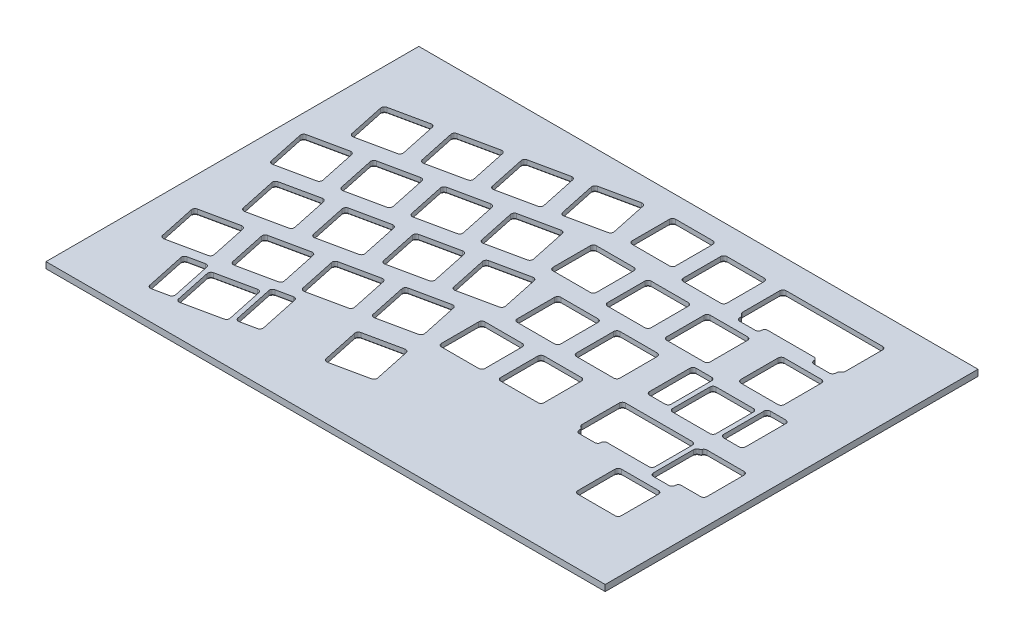
SolidWorks part; units mm, degrees
ref_plane "Front Plane" through (0, 0, 0) normal (0, 0, 1) x (1, 0, 0)
ref_plane "Top Plane" through (0, 0, 0) normal (0, 1, 0) x (1, 0, 0)
ref_plane "Right Plane" through (0, 0, 0) normal (1, 0, 0) x (0, 0, -1)
sketch "Sketch1" plane through (0, 0, 0) normal (0, 1, 0) x (1, 0, 0)
  line L1 (-5, -3) -> (175, -3)
  line L2 (-5, -3) -> (-5, 117)
  line L3 (-5, 117) -> (175, 117)
  line L4 (175, -3) -> (175, 117)
  line L5 (-5, -3) -> (175, 117) construction
  line L6 (-5, 117) -> (175, -3) construction
  point P5 (85, 57)
  line B0 (3.9344, 34.8314) -> (6.4293, 23.0936)
  line B1 (7.6154, 22.3234) -> (19.3531, 24.8183)
  line B2 (17.6284, 37.7422) -> (20.1234, 26.0044)
  line B3 (4.7046, 36.0175) -> (16.4424, 38.5124)
  line B4 (9.2944, 55.4414) -> (11.7893, 43.7036)
  line B5 (12.9754, 42.9334) -> (24.7131, 45.4283)
  line B6 (22.9884, 58.3522) -> (25.4834, 46.6144)
  line B7 (10.0646, 56.6275) -> (21.8024, 59.1224)
  line B8 (0.6744, 73.0914) -> (3.1693, 61.3536)
  line B9 (4.3554, 60.5834) -> (16.0931, 63.0783)
  line B10 (14.3684, 76.0022) -> (16.8634, 64.2644)
  line B11 (1.4446, 74.2775) -> (13.1824, 76.7724)
  line B12 (6.0344, 93.7014) -> (8.5293, 81.9636)
  line B13 (9.7154, 81.1934) -> (21.4531, 83.6883)
  line B14 (19.7284, 96.6122) -> (22.2234, 84.8744)
  line B15 (6.8046, 94.8875) -> (18.5424, 97.3824)
  line B16 (22.5681, 38.7921) -> (25.063, 27.0543)
  line B17 (26.2491, 26.2841) -> (37.9868, 28.7791)
  line B18 (36.2621, 41.7029) -> (38.7571, 29.9651)
  line B19 (23.3383, 39.9782) -> (35.0761, 42.4731)
  line B20 (27.9281, 59.4021) -> (30.423, 47.6643)
  line B21 (31.6091, 46.8941) -> (43.3468, 49.3891)
  line B22 (41.6221, 62.3129) -> (44.1171, 50.5751)
  line B23 (28.6983, 60.5882) -> (40.4361, 63.0831)
  line B24 (19.3081, 77.0521) -> (21.803, 65.3143)
  line B25 (22.9891, 64.5441) -> (34.7268, 67.0391)
  line B26 (33.0021, 79.9629) -> (35.4971, 68.2251)
  line B27 (20.0783, 78.2382) -> (31.8161, 80.7331)
  line B28 (24.6681, 97.6621) -> (27.163, 85.9243)
  line B29 (28.3491, 85.1541) -> (40.0868, 87.6491)
  line B30 (38.3621, 100.5729) -> (40.8571, 88.8351)
  line B31 (25.4383, 98.8482) -> (37.1761, 101.3431)
  line B32 (41.2018, 42.7528) -> (43.6967, 31.0151)
  line B33 (44.8828, 30.2448) -> (56.6206, 32.7398)
  line B34 (54.8959, 45.6636) -> (57.3908, 33.9258)
  line B35 (41.972, 43.9389) -> (53.7098, 46.4338)
  line B36 (46.5618, 63.3628) -> (49.0567, 51.6251)
  line B37 (50.2428, 50.8548) -> (61.9806, 53.3498)
  line B38 (60.2559, 66.2736) -> (62.7508, 54.5358)
  line B39 (47.332, 64.5489) -> (59.0698, 67.0438)
  line B40 (37.9418, 81.0128) -> (40.4367, 69.2751)
  line B41 (41.6228, 68.5048) -> (53.3606, 70.9998)
  line B42 (51.6359, 83.9236) -> (54.1308, 72.1858)
  line B43 (38.712, 82.1989) -> (50.4498, 84.6938)
  line B44 (43.3018, 101.6228) -> (45.7967, 89.8851)
  line B45 (46.9828, 89.1148) -> (58.7206, 91.6098)
  line B46 (56.9959, 104.5336) -> (59.4908, 92.7958)
  line B47 (44.072, 102.8089) -> (55.8098, 105.3038)
  line B48 (24.2355, 19.6636) -> (26.7304, 7.9258)
  line B49 (27.9165, 7.1555) -> (39.6543, 9.6505)
  line B50 (37.9296, 22.5743) -> (40.4245, 10.8365)
  line B51 (25.0057, 20.8496) -> (36.7435, 23.3446)
  line B52 (64.6455, 26.7236) -> (67.1404, 14.9858)
  line B53 (68.3265, 14.2155) -> (80.0643, 16.7105)
  line B54 (78.3396, 29.6343) -> (80.8345, 17.8965)
  line B55 (65.4157, 27.9096) -> (77.1535, 30.4046)
  line B56 (59.8355, 46.7136) -> (62.3304, 34.9758)
  line B57 (63.5165, 34.2055) -> (75.2543, 36.7005)
  line B58 (73.5296, 49.6243) -> (76.0245, 37.8865)
  line B59 (60.6057, 47.8996) -> (72.3435, 50.3946)
  line B60 (65.1955, 67.3236) -> (67.6904, 55.5858)
  line B61 (68.8765, 54.8155) -> (80.6143, 57.3105)
  line B62 (78.8896, 70.2343) -> (81.3845, 58.4965)
  line B63 (65.9657, 68.5096) -> (77.7035, 71.0046)
  line B64 (61.9355, 105.5836) -> (64.4304, 93.8458)
  line B65 (65.6165, 93.0755) -> (77.3543, 95.5705)
  line B66 (75.6296, 108.4943) -> (78.1245, 96.7565)
  line B67 (62.7057, 106.7696) -> (74.4435, 109.2646)
  line B68 (56.5755, 84.9736) -> (59.0704, 73.2358)
  line B69 (60.2565, 72.4655) -> (71.9943, 74.9605)
  line B70 (70.2696, 87.8843) -> (72.7645, 76.1465)
  line B71 (57.3457, 86.1596) -> (69.0835, 88.6546)
  line B72 (83.53, 109.15) -> (83.53, 97.15)
  line B73 (84.53, 96.15) -> (96.53, 96.15)
  line B74 (97.53, 109.15) -> (97.53, 97.15)
  line B75 (84.53, 110.15) -> (96.53, 110.15)
  line B76 (102.16, 107.01) -> (102.16, 95.01)
  line B77 (103.16, 94.01) -> (115.16, 94.01)
  line B78 (116.16, 107.01) -> (116.16, 95.01)
  line B79 (103.16, 108.01) -> (115.16, 108.01)
  line B80 (139.67, 87.96) -> (139.67, 75.96)
  line B81 (140.67, 74.96) -> (152.67, 74.96)
  line B82 (153.67, 87.96) -> (153.67, 75.96)
  line B83 (140.67, 88.96) -> (152.67, 88.96)
  line B84 (78.17, 89.02) -> (78.17, 77.02)
  line B85 (79.17, 76.02) -> (91.17, 76.02)
  line B86 (92.17, 89.02) -> (92.17, 77.02)
  line B87 (79.17, 90.02) -> (91.17, 90.02)
  line B88 (115.85, 87.96) -> (115.85, 75.96)
  line B89 (116.85, 74.96) -> (128.85, 74.96)
  line B90 (129.85, 87.96) -> (129.85, 75.96)
  line B91 (116.85, 88.96) -> (128.85, 88.96)
  line B92 (86.79, 68.91) -> (86.79, 56.91)
  line B93 (87.79, 55.91) -> (99.79, 55.91)
  line B94 (100.79, 68.91) -> (100.79, 56.91)
  line B95 (87.79, 69.91) -> (99.79, 69.91)
  line B96 (96.8, 87.96) -> (96.8, 75.96)
  line B97 (97.8, 74.96) -> (109.8, 74.96)
  line B98 (110.8, 87.96) -> (110.8, 75.96)
  line B99 (97.8, 88.96) -> (109.8, 88.96)
  line B100 (81.43, 49.86) -> (81.43, 37.86)
  line B101 (82.43, 36.86) -> (94.43, 36.86)
  line B102 (95.43, 49.86) -> (95.43, 37.86)
  line B103 (82.43, 50.86) -> (94.43, 50.86)
  line B104 (136.79, 68.91) -> (136.79, 56.91)
  line B105 (137.79, 55.91) -> (149.79, 55.91)
  line B106 (150.79, 68.91) -> (150.79, 56.91)
  line B107 (137.79, 69.91) -> (149.79, 69.91)
  line B108 (105.84, 68.91) -> (105.84, 56.91)
  line B109 (106.84, 55.91) -> (118.84, 55.91)
  line B110 (119.84, 68.91) -> (119.84, 56.91)
  line B111 (106.84, 69.91) -> (118.84, 69.91)
  line B112 (144.4256, 30.762) -> (144.4256, 18.762)
  line B113 (145.4256, 17.762) -> (157.4256, 17.762)
  line B114 (158.4256, 30.762) -> (158.4256, 18.762)
  line B115 (145.4256, 31.762) -> (157.4256, 31.762)
  line B116 (100.48, 49.86) -> (100.48, 37.86)
  line B117 (101.48, 36.86) -> (113.48, 36.86)
  line B118 (114.48, 49.86) -> (114.48, 37.86)
  line B119 (101.48, 50.86) -> (113.48, 50.86)
  line B120 (151.638, 48.86) -> (151.638, 35.86)
  line B121 (152.638, 34.86) -> (157.638, 34.86)
  line B122 (158.638, 35.86) -> (158.638, 36.86)
  line B123 (158.638, 36.86) -> (165.8688, 36.86)
  line B124 (166.8688, 49.86) -> (166.8688, 37.86)
  line B125 (153.8688, 50.86) -> (165.8688, 50.86)
  line B126 (152.8688, 49.86) -> (152.638, 49.86)
  line B127 (128.762, 34.86) -> (133.762, 34.86)
  line B128 (134.762, 35.86) -> (134.762, 36.86)
  line B129 (134.762, 36.86) -> (149.2, 36.86)
  line B130 (150.2, 49.86) -> (150.2, 37.86)
  line B131 (127.675, 50.86) -> (149.2, 50.86)
  line B132 (126.675, 49.86) -> (126.675, 37.86)
  line B133 (127.675, 36.86) -> (127.762, 36.86)
  line B134 (127.762, 36.86) -> (127.762, 35.86)
  line B135 (15.5661, 19.8655) -> (18.2689, 7.1496)
  line B136 (19.455, 6.3793) -> (24.3457, 7.4189)
  line B137 (25.1159, 8.605) -> (22.4131, 21.3209)
  line B138 (21.227, 22.0911) -> (16.3363, 21.0515)
  line B139 (38.9203, 24.8296) -> (41.6232, 12.1137)
  line B140 (42.8092, 11.3434) -> (47.7, 12.383)
  line B141 (48.4702, 13.5691) -> (45.7673, 26.285)
  line B142 (44.5813, 27.0552) -> (39.6906, 26.0156)
  line B143 (128.352, 70.91) -> (128.352, 57.91)
  line B144 (129.352, 56.91) -> (134.352, 56.91)
  line B145 (135.352, 57.91) -> (135.352, 70.91)
  line B146 (134.352, 71.91) -> (129.352, 71.91)
  line B147 (147.173, 92.01) -> (152.173, 92.01)
  line B148 (153.173, 93.01) -> (153.173, 94.01)
  line B149 (153.173, 94.01) -> (153.26, 94.01)
  line B150 (154.26, 107.01) -> (154.26, 95.01)
  line B151 (122.21, 108.01) -> (153.26, 108.01)
  line B152 (121.21, 107.01) -> (121.21, 95.01)
  line B153 (122.21, 94.01) -> (122.297, 94.01)
  line B154 (122.297, 94.01) -> (122.297, 93.01)
  line B155 (123.297, 92.01) -> (128.297, 92.01)
  line B156 (129.297, 93.01) -> (129.297, 94.01)
  line B157 (129.297, 94.01) -> (146.173, 94.01)
  line B158 (146.173, 94.01) -> (146.173, 93.01)
  line B159 (152.228, 70.91) -> (152.228, 57.91)
  line B160 (153.228, 56.91) -> (158.228, 56.91)
  line B161 (159.228, 57.91) -> (159.228, 70.91)
  line B162 (158.228, 71.91) -> (153.228, 71.91)
  arc B163 (6.4293, 23.0936) -> (7.6154, 22.3234) centre (7.4074, 23.3015) ccw
  arc B164 (19.3531, 24.8183) -> (20.1234, 26.0044) centre (19.1452, 25.7965) ccw
  arc B165 (17.6284, 37.7422) -> (16.4424, 38.5124) centre (16.6503, 37.5343) ccw
  arc B166 (4.7046, 36.0175) -> (3.9344, 34.8314) centre (4.9125, 35.0393) ccw
  arc B167 (11.7893, 43.7036) -> (12.9754, 42.9334) centre (12.7674, 43.9115) ccw
  arc B168 (24.7131, 45.4283) -> (25.4834, 46.6144) centre (24.5052, 46.4065) ccw
  arc B169 (22.9884, 58.3522) -> (21.8024, 59.1224) centre (22.0103, 58.1443) ccw
  arc B170 (10.0646, 56.6275) -> (9.2944, 55.4414) centre (10.2725, 55.6493) ccw
  arc B171 (3.1693, 61.3536) -> (4.3554, 60.5834) centre (4.1474, 61.5615) ccw
  arc B172 (16.0931, 63.0783) -> (16.8634, 64.2644) centre (15.8852, 64.0565) ccw
  arc B173 (14.3684, 76.0022) -> (13.1824, 76.7724) centre (13.3903, 75.7943) ccw
  arc B174 (1.4446, 74.2775) -> (0.6744, 73.0914) centre (1.6525, 73.2993) ccw
  arc B175 (8.5293, 81.9636) -> (9.7154, 81.1934) centre (9.5074, 82.1715) ccw
  arc B176 (21.4531, 83.6883) -> (22.2234, 84.8744) centre (21.2452, 84.6665) ccw
  arc B177 (19.7284, 96.6122) -> (18.5424, 97.3824) centre (18.7503, 96.4043) ccw
  arc B178 (6.8046, 94.8875) -> (6.0344, 93.7014) centre (7.0125, 93.9093) ccw
  arc B179 (25.063, 27.0543) -> (26.2491, 26.2841) centre (26.0412, 27.2623) ccw
  arc B180 (37.9868, 28.7791) -> (38.7571, 29.9651) centre (37.7789, 29.7572) ccw
  arc B181 (36.2621, 41.7029) -> (35.0761, 42.4731) centre (35.284, 41.495) ccw
  arc B182 (23.3383, 39.9782) -> (22.5681, 38.7921) centre (23.5462, 39) ccw
  arc B183 (30.423, 47.6643) -> (31.6091, 46.8941) centre (31.4012, 47.8723) ccw
  arc B184 (43.3468, 49.3891) -> (44.1171, 50.5751) centre (43.1389, 50.3672) ccw
  arc B185 (41.6221, 62.3129) -> (40.4361, 63.0831) centre (40.644, 62.105) ccw
  arc B186 (28.6983, 60.5882) -> (27.9281, 59.4021) centre (28.9062, 59.61) ccw
  arc B187 (21.803, 65.3143) -> (22.9891, 64.5441) centre (22.7812, 65.5223) ccw
  arc B188 (34.7268, 67.0391) -> (35.4971, 68.2251) centre (34.5189, 68.0172) ccw
  arc B189 (33.0021, 79.9629) -> (31.8161, 80.7331) centre (32.024, 79.755) ccw
  arc B190 (20.0783, 78.2382) -> (19.3081, 77.0521) centre (20.2862, 77.26) ccw
  arc B191 (27.163, 85.9243) -> (28.3491, 85.1541) centre (28.1412, 86.1323) ccw
  arc B192 (40.0868, 87.6491) -> (40.8571, 88.8351) centre (39.8789, 88.6272) ccw
  arc B193 (38.3621, 100.5729) -> (37.1761, 101.3431) centre (37.384, 100.365) ccw
  arc B194 (25.4383, 98.8482) -> (24.6681, 97.6621) centre (25.6462, 97.87) ccw
  arc B195 (43.6967, 31.0151) -> (44.8828, 30.2448) centre (44.6749, 31.223) ccw
  arc B196 (56.6206, 32.7398) -> (57.3908, 33.9258) centre (56.4126, 33.7179) ccw
  arc B197 (54.8959, 45.6636) -> (53.7098, 46.4338) centre (53.9177, 45.4557) ccw
  arc B198 (41.972, 43.9389) -> (41.2018, 42.7528) centre (42.1799, 42.9607) ccw
  arc B199 (49.0567, 51.6251) -> (50.2428, 50.8548) centre (50.0349, 51.833) ccw
  arc B200 (61.9806, 53.3498) -> (62.7508, 54.5358) centre (61.7726, 54.3279) ccw
  arc B201 (60.2559, 66.2736) -> (59.0698, 67.0438) centre (59.2777, 66.0657) ccw
  arc B202 (47.332, 64.5489) -> (46.5618, 63.3628) centre (47.5399, 63.5707) ccw
  arc B203 (40.4367, 69.2751) -> (41.6228, 68.5048) centre (41.4149, 69.483) ccw
  arc B204 (53.3606, 70.9998) -> (54.1308, 72.1858) centre (53.1526, 71.9779) ccw
  arc B205 (51.6359, 83.9236) -> (50.4498, 84.6938) centre (50.6577, 83.7157) ccw
  arc B206 (38.712, 82.1989) -> (37.9418, 81.0128) centre (38.9199, 81.2207) ccw
  arc B207 (45.7967, 89.8851) -> (46.9828, 89.1148) centre (46.7749, 90.093) ccw
  arc B208 (58.7206, 91.6098) -> (59.4908, 92.7958) centre (58.5126, 92.5879) ccw
  arc B209 (56.9959, 104.5336) -> (55.8098, 105.3038) centre (56.0177, 104.3257) ccw
  arc B210 (44.072, 102.8089) -> (43.3018, 101.6228) centre (44.2799, 101.8307) ccw
  arc B211 (26.7304, 7.9258) -> (27.9165, 7.1555) centre (27.7086, 8.1337) ccw
  arc B212 (39.6543, 9.6505) -> (40.4245, 10.8365) centre (39.4464, 10.6286) ccw
  arc B213 (37.9296, 22.5743) -> (36.7435, 23.3446) centre (36.9514, 22.3664) ccw
  arc B214 (25.0057, 20.8496) -> (24.2355, 19.6636) centre (25.2136, 19.8715) ccw
  arc B215 (67.1404, 14.9858) -> (68.3265, 14.2155) centre (68.1186, 15.1937) ccw
  arc B216 (80.0643, 16.7105) -> (80.8345, 17.8965) centre (79.8564, 17.6886) ccw
  arc B217 (78.3396, 29.6343) -> (77.1535, 30.4046) centre (77.3614, 29.4264) ccw
  arc B218 (65.4157, 27.9096) -> (64.6455, 26.7236) centre (65.6236, 26.9315) ccw
  arc B219 (62.3304, 34.9758) -> (63.5165, 34.2055) centre (63.3086, 35.1837) ccw
  arc B220 (75.2543, 36.7005) -> (76.0245, 37.8865) centre (75.0464, 37.6786) ccw
  arc B221 (73.5296, 49.6243) -> (72.3435, 50.3946) centre (72.5514, 49.4164) ccw
  arc B222 (60.6057, 47.8996) -> (59.8355, 46.7136) centre (60.8136, 46.9215) ccw
  arc B223 (67.6904, 55.5858) -> (68.8765, 54.8155) centre (68.6686, 55.7937) ccw
  arc B224 (80.6143, 57.3105) -> (81.3845, 58.4965) centre (80.4064, 58.2886) ccw
  arc B225 (78.8896, 70.2343) -> (77.7035, 71.0046) centre (77.9114, 70.0264) ccw
  arc B226 (65.9657, 68.5096) -> (65.1955, 67.3236) centre (66.1736, 67.5315) ccw
  arc B227 (64.4304, 93.8458) -> (65.6165, 93.0755) centre (65.4086, 94.0537) ccw
  arc B228 (77.3543, 95.5705) -> (78.1245, 96.7565) centre (77.1464, 96.5486) ccw
  arc B229 (75.6296, 108.4943) -> (74.4435, 109.2646) centre (74.6514, 108.2864) ccw
  arc B230 (62.7057, 106.7696) -> (61.9355, 105.5836) centre (62.9136, 105.7915) ccw
  arc B231 (59.0704, 73.2358) -> (60.2565, 72.4655) centre (60.0486, 73.4437) ccw
  arc B232 (71.9943, 74.9605) -> (72.7645, 76.1465) centre (71.7864, 75.9386) ccw
  arc B233 (70.2696, 87.8843) -> (69.0835, 88.6546) centre (69.2914, 87.6764) ccw
  arc B234 (57.3457, 86.1596) -> (56.5755, 84.9736) centre (57.5536, 85.1815) ccw
  arc B235 (83.53, 97.15) -> (84.53, 96.15) centre (84.53, 97.15) ccw
  arc B236 (96.53, 96.15) -> (97.53, 97.15) centre (96.53, 97.15) ccw
  arc B237 (97.53, 109.15) -> (96.53, 110.15) centre (96.53, 109.15) ccw
  arc B238 (84.53, 110.15) -> (83.53, 109.15) centre (84.53, 109.15) ccw
  arc B239 (102.16, 95.01) -> (103.16, 94.01) centre (103.16, 95.01) ccw
  arc B240 (115.16, 94.01) -> (116.16, 95.01) centre (115.16, 95.01) ccw
  arc B241 (116.16, 107.01) -> (115.16, 108.01) centre (115.16, 107.01) ccw
  arc B242 (103.16, 108.01) -> (102.16, 107.01) centre (103.16, 107.01) ccw
  arc B243 (139.67, 75.96) -> (140.67, 74.96) centre (140.67, 75.96) ccw
  arc B244 (152.67, 74.96) -> (153.67, 75.96) centre (152.67, 75.96) ccw
  arc B245 (153.67, 87.96) -> (152.67, 88.96) centre (152.67, 87.96) ccw
  arc B246 (140.67, 88.96) -> (139.67, 87.96) centre (140.67, 87.96) ccw
  arc B247 (78.17, 77.02) -> (79.17, 76.02) centre (79.17, 77.02) ccw
  arc B248 (91.17, 76.02) -> (92.17, 77.02) centre (91.17, 77.02) ccw
  arc B249 (92.17, 89.02) -> (91.17, 90.02) centre (91.17, 89.02) ccw
  arc B250 (79.17, 90.02) -> (78.17, 89.02) centre (79.17, 89.02) ccw
  arc B251 (115.85, 75.96) -> (116.85, 74.96) centre (116.85, 75.96) ccw
  arc B252 (128.85, 74.96) -> (129.85, 75.96) centre (128.85, 75.96) ccw
  arc B253 (129.85, 87.96) -> (128.85, 88.96) centre (128.85, 87.96) ccw
  arc B254 (116.85, 88.96) -> (115.85, 87.96) centre (116.85, 87.96) ccw
  arc B255 (86.79, 56.91) -> (87.79, 55.91) centre (87.79, 56.91) ccw
  arc B256 (99.79, 55.91) -> (100.79, 56.91) centre (99.79, 56.91) ccw
  arc B257 (100.79, 68.91) -> (99.79, 69.91) centre (99.79, 68.91) ccw
  arc B258 (87.79, 69.91) -> (86.79, 68.91) centre (87.79, 68.91) ccw
  arc B259 (96.8, 75.96) -> (97.8, 74.96) centre (97.8, 75.96) ccw
  arc B260 (109.8, 74.96) -> (110.8, 75.96) centre (109.8, 75.96) ccw
  arc B261 (110.8, 87.96) -> (109.8, 88.96) centre (109.8, 87.96) ccw
  arc B262 (97.8, 88.96) -> (96.8, 87.96) centre (97.8, 87.96) ccw
  arc B263 (81.43, 37.86) -> (82.43, 36.86) centre (82.43, 37.86) ccw
  arc B264 (94.43, 36.86) -> (95.43, 37.86) centre (94.43, 37.86) ccw
  arc B265 (95.43, 49.86) -> (94.43, 50.86) centre (94.43, 49.86) ccw
  arc B266 (82.43, 50.86) -> (81.43, 49.86) centre (82.43, 49.86) ccw
  arc B267 (136.79, 56.91) -> (137.79, 55.91) centre (137.79, 56.91) ccw
  arc B268 (149.79, 55.91) -> (150.79, 56.91) centre (149.79, 56.91) ccw
  arc B269 (150.79, 68.91) -> (149.79, 69.91) centre (149.79, 68.91) ccw
  arc B270 (137.79, 69.91) -> (136.79, 68.91) centre (137.79, 68.91) ccw
  arc B271 (105.84, 56.91) -> (106.84, 55.91) centre (106.84, 56.91) ccw
  arc B272 (118.84, 55.91) -> (119.84, 56.91) centre (118.84, 56.91) ccw
  arc B273 (119.84, 68.91) -> (118.84, 69.91) centre (118.84, 68.91) ccw
  arc B274 (106.84, 69.91) -> (105.84, 68.91) centre (106.84, 68.91) ccw
  arc B275 (144.4256, 18.762) -> (145.4256, 17.762) centre (145.4256, 18.762) ccw
  arc B276 (157.4256, 17.762) -> (158.4256, 18.762) centre (157.4256, 18.762) ccw
  arc B277 (158.4256, 30.762) -> (157.4256, 31.762) centre (157.4256, 30.762) ccw
  arc B278 (145.4256, 31.762) -> (144.4256, 30.762) centre (145.4256, 30.762) ccw
  arc B279 (100.48, 37.86) -> (101.48, 36.86) centre (101.48, 37.86) ccw
  arc B280 (113.48, 36.86) -> (114.48, 37.86) centre (113.48, 37.86) ccw
  arc B281 (114.48, 49.86) -> (113.48, 50.86) centre (113.48, 49.86) ccw
  arc B282 (101.48, 50.86) -> (100.48, 49.86) centre (101.48, 49.86) ccw
  arc B283 (152.638, 49.86) -> (151.638, 48.86) centre (152.638, 48.86) ccw
  arc B284 (151.638, 35.86) -> (152.638, 34.86) centre (152.638, 35.86) ccw
  arc B285 (157.638, 34.86) -> (158.638, 35.86) centre (157.638, 35.86) ccw
  arc B286 (165.8688, 36.86) -> (166.8688, 37.86) centre (165.8687, 37.86) ccw
  arc B287 (166.8688, 49.86) -> (165.8688, 50.86) centre (165.8687, 49.86) ccw
  arc B288 (153.8688, 50.86) -> (152.8688, 49.86) centre (153.8688, 49.86) ccw
  arc B289 (127.762, 35.86) -> (128.762, 34.86) centre (128.762, 35.86) ccw
  arc B290 (133.762, 34.86) -> (134.762, 35.86) centre (133.762, 35.86) ccw
  arc B291 (149.2, 36.86) -> (150.2, 37.86) centre (149.2, 37.86) ccw
  arc B292 (150.2, 49.86) -> (149.2, 50.86) centre (149.2, 49.86) ccw
  arc B293 (127.675, 50.86) -> (126.675, 49.86) centre (127.675, 49.86) ccw
  arc B294 (126.675, 37.86) -> (127.675, 36.86) centre (127.675, 37.86) ccw
  arc B295 (18.2689, 7.1496) -> (19.455, 6.3793) centre (19.2471, 7.3575) ccw
  arc B296 (24.3457, 7.4189) -> (25.1159, 8.605) centre (24.1378, 8.397) ccw
  arc B297 (22.4131, 21.3209) -> (21.227, 22.0911) centre (21.4349, 21.113) ccw
  arc B298 (16.3363, 21.0515) -> (15.5661, 19.8655) centre (16.5442, 20.0734) ccw
  arc B299 (41.6232, 12.1137) -> (42.8092, 11.3434) centre (42.6013, 12.3216) ccw
  arc B300 (47.7, 12.383) -> (48.4702, 13.5691) centre (47.4921, 13.3611) ccw
  arc B301 (45.7673, 26.285) -> (44.5813, 27.0552) centre (44.7892, 26.0771) ccw
  arc B302 (39.6906, 26.0156) -> (38.9203, 24.8296) centre (39.8985, 25.0375) ccw
  arc B303 (128.352, 57.91) -> (129.352, 56.91) centre (129.352, 57.91) ccw
  arc B304 (134.352, 56.91) -> (135.352, 57.91) centre (134.352, 57.91) ccw
  arc B305 (135.352, 70.91) -> (134.352, 71.91) centre (134.352, 70.91) ccw
  arc B306 (129.352, 71.91) -> (128.352, 70.91) centre (129.352, 70.91) ccw
  arc B307 (146.173, 93.01) -> (147.173, 92.01) centre (147.173, 93.01) ccw
  arc B308 (152.173, 92.01) -> (153.173, 93.01) centre (152.173, 93.01) ccw
  arc B309 (153.26, 94.01) -> (154.26, 95.01) centre (153.26, 95.01) ccw
  arc B310 (154.26, 107.01) -> (153.26, 108.01) centre (153.26, 107.01) ccw
  arc B311 (122.21, 108.01) -> (121.21, 107.01) centre (122.21, 107.01) ccw
  arc B312 (121.21, 95.01) -> (122.21, 94.01) centre (122.21, 95.01) ccw
  arc B313 (122.297, 93.01) -> (123.297, 92.01) centre (123.297, 93.01) ccw
  arc B314 (128.297, 92.01) -> (129.297, 93.01) centre (128.297, 93.01) ccw
  arc B315 (152.228, 57.91) -> (153.228, 56.91) centre (153.228, 57.91) ccw
  arc B316 (158.228, 56.91) -> (159.228, 57.91) centre (158.228, 57.91) ccw
  arc B317 (159.228, 70.91) -> (158.228, 71.91) centre (158.228, 70.91) ccw
  arc B318 (153.228, 71.91) -> (152.228, 70.91) centre (153.228, 70.91) ccw
  dimension "D1" = 180
  dimension "D2" = 120
  dimension "D3" = 3
  dimension "D4" = 5
sketch_block_instance "alice-split-right-side-1"
sketch_block "alice-split-right-side"
extrude "Boss-Extrude1" add sketch "Sketch1" along normal mid plane 2
fillet "Fillet1" radius 1 8 edges at (122.297, 0, -94.01) (153.173, 0, -94.01) (129.297, 0, -94.01) (146.173, 0, -94.01) (152.8688, 0, -49.86) (158.638, 0, -36.86) (134.762, 0, -36.86) (127.762, 0, -36.86)
chamfer "Chamfer1" distance 0.5 angle 45 319 edges at (21.9003, -1, -6.8991) (24.9765, -1, -7.8524) (18.7024, -1, -6.5188) (23.7645, -1, -14.9629) (16.9175, -1, -13.5075) (21.9796, -1, -21.9516) (15.7055, -1, -20.618) (18.7817, -1, -21.5713) (33.7854, -1, -8.403) (40.285, -1, -10.084) (27.1639, -1, -7.295) (39.177, -1, -16.7054) (25.483, -1, -13.7947) (37.4961, -1, -23.2051) (24.375, -1, -20.4161) (30.8746, -1, -22.0971) (45.2546, -1, -11.8632) (48.3307, -1, -12.8165) (42.0567, -1, -11.4829) (47.1188, -1, -19.927) (40.2717, -1, -18.4716) (45.3338, -1, -26.9157) (39.0598, -1, -25.5821) (42.1359, -1, -26.5354) (74.1954, -1, -15.463) (80.695, -1, -17.144) (67.5739, -1, -14.355) (79.587, -1, -23.7654) (65.893, -1, -20.8547) (77.9061, -1, -30.2651) (64.785, -1, -27.4761) (71.2846, -1, -29.1571) (151.4256, -1, -17.762) (158.1327, -1, -18.0549) (144.7185, -1, -18.0549) (158.4256, -1, -24.762) (144.4256, -1, -24.762) (158.1327, -1, -31.4692) (144.7185, -1, -31.4692) (151.4256, -1, -31.762) (158.3451, -1, -35.1529) (155.138, -1, -34.86) (158.9309, -1, -36.5672) (151.9309, -1, -35.1529) (162.7534, -1, -36.86) (151.638, -1, -42.36) (166.5759, -1, -37.1529) (151.8407, -1, -49.4637) (166.8688, -1, -43.86) (152.7261, -1, -50.009) (166.5759, -1, -50.5672) (153.3503, -1, -50.7152) (159.8688, -1, -50.86) (131.262, -1, -34.86) (134.4691, -1, -35.1529) (128.0549, -1, -35.1529) (135.0549, -1, -36.5672) (127.762, -1, -35.9703) (142.481, -1, -36.86) (127.6154, -1, -36.6019) (149.9071, -1, -37.1529) (126.8216, -1, -37.3388) (150.2, -1, -43.86) (126.675, -1, -43.86) (149.9071, -1, -50.5672) (126.9679, -1, -50.5672) (138.4375, -1, -50.86) (107.48, -1, -36.86) (114.1871, -1, -37.1529) (100.7729, -1, -37.1529) (114.48, -1, -43.86) (100.48, -1, -43.86) (114.1871, -1, -50.5672) (100.7729, -1, -50.5672) (107.48, -1, -50.86) (88.43, -1, -36.86) (95.1371, -1, -37.1529) (81.7229, -1, -37.1529) (95.43, -1, -43.86) (81.43, -1, -43.86) (95.1371, -1, -50.5672) (81.7229, -1, -50.5672) (88.43, -1, -50.86) (69.3854, -1, -35.453) (75.885, -1, -37.134) (62.7639, -1, -34.345) (74.777, -1, -43.7554) (61.083, -1, -40.8447) (73.0961, -1, -50.2551) (59.975, -1, -47.4661) (66.4746, -1, -49.1471) (50.7517, -1, -31.4923) (57.2513, -1, -33.1733) (44.1302, -1, -30.3843) (56.1433, -1, -39.7947) (42.4493, -1, -36.8839) (54.4623, -1, -46.2944) (41.3413, -1, -43.5054) (47.8409, -1, -45.1864) (32.118, -1, -27.5316) (38.6176, -1, -29.2126) (25.4965, -1, -26.4236) (37.5096, -1, -35.834) (23.8155, -1, -32.9232) (35.8286, -1, -42.3336) (22.7076, -1, -39.5447) (29.2072, -1, -41.2256) (13.4842, -1, -23.5709) (19.9839, -1, -25.2518) (6.8628, -1, -22.4629) (18.8759, -1, -31.8733) (5.1818, -1, -28.9625) (17.1949, -1, -38.3729) (4.0738, -1, -35.584) (10.5735, -1, -37.2649) (18.8442, -1, -44.1809) (25.3439, -1, -45.8618) (12.2228, -1, -43.0729) (24.2359, -1, -52.4833) (10.5418, -1, -49.5725) (22.5549, -1, -58.9829) (9.4338, -1, -56.194) (15.9335, -1, -57.8749) (37.478, -1, -48.1416) (43.9776, -1, -49.8226) (30.8565, -1, -47.0336) (42.8696, -1, -56.444) (29.1755, -1, -53.5332) (41.1886, -1, -62.9436) (28.0676, -1, -60.1547) (34.5672, -1, -61.8356) (56.1117, -1, -52.1023) (62.6113, -1, -53.7833) (49.4902, -1, -50.9943) (61.5033, -1, -60.4047) (47.8093, -1, -57.4939) (59.8223, -1, -66.9044) (46.7013, -1, -64.1154) (53.2009, -1, -65.7964) (74.7454, -1, -56.063) (81.245, -1, -57.744) (68.1239, -1, -54.955) (80.137, -1, -64.3654) (66.443, -1, -61.4547) (78.4561, -1, -70.8651) (65.335, -1, -68.0761) (71.8346, -1, -69.7571) (93.79, -1, -55.91) (100.4971, -1, -56.2029) (87.0829, -1, -56.2029) (100.79, -1, -62.91) (86.79, -1, -62.91) (100.4971, -1, -69.6172) (87.0829, -1, -69.6172) (93.79, -1, -69.91) (112.84, -1, -55.91) (119.5471, -1, -56.2029) (106.1329, -1, -56.2029) (119.84, -1, -62.91) (105.84, -1, -62.91) (119.5471, -1, -69.6172) (106.1329, -1, -69.6172) (112.84, -1, -69.91) (131.852, -1, -56.91) (135.0591, -1, -57.2029) (128.6449, -1, -57.2029) (135.352, -1, -64.41) (128.352, -1, -64.41) (135.0591, -1, -71.6172) (128.6449, -1, -71.6172) (131.852, -1, -71.91) (143.79, -1, -55.91) (150.4971, -1, -56.2029) (137.0829, -1, -56.2029) (150.79, -1, -62.91) (136.79, -1, -62.91) (150.4971, -1, -69.6172) (137.0829, -1, -69.6172) (143.79, -1, -69.91) (155.728, -1, -56.91) (158.9351, -1, -57.2029) (152.5209, -1, -57.2029) (159.228, -1, -64.41) (152.228, -1, -64.41) (158.9351, -1, -71.6172) (152.5209, -1, -71.6172) (155.728, -1, -71.91) (146.67, -1, -74.96) (153.3771, -1, -75.2529) (139.9629, -1, -75.2529) (153.67, -1, -81.96) (139.67, -1, -81.96) (153.3771, -1, -88.6672) (139.9629, -1, -88.6672) (146.67, -1, -88.96) (122.85, -1, -74.96) (129.5571, -1, -75.2529) (116.1429, -1, -75.2529) (129.85, -1, -81.96) (115.85, -1, -81.96) (129.5571, -1, -88.6672) (116.1429, -1, -88.6672) (122.85, -1, -88.96) (103.8, -1, -74.96) (110.5071, -1, -75.2529) (97.0929, -1, -75.2529) (110.8, -1, -81.96) (96.8, -1, -81.96) (110.5071, -1, -88.6672) (97.0929, -1, -88.6672) (103.8, -1, -88.96) (85.17, -1, -76.02) (91.8771, -1, -76.3129) (78.4629, -1, -76.3129) (92.17, -1, -83.02) (78.17, -1, -83.02) (91.8771, -1, -89.7272) (78.4629, -1, -89.7272) (85.17, -1, -90.02) (66.1254, -1, -73.713) (72.625, -1, -75.394) (59.5039, -1, -72.605) (71.517, -1, -82.0154) (57.823, -1, -79.1047) (69.8361, -1, -88.5151) (56.715, -1, -85.7261) (63.2146, -1, -87.4071) (47.4917, -1, -69.7523) (53.9913, -1, -71.4333) (40.8702, -1, -68.6443) (52.8833, -1, -78.0547) (39.1893, -1, -75.1439) (51.2023, -1, -84.5544) (38.0813, -1, -81.7654) (44.5809, -1, -83.4464) (28.858, -1, -65.7916) (35.3576, -1, -67.4726) (22.2365, -1, -64.6836) (34.2496, -1, -74.094) (20.5555, -1, -71.1832) (32.5686, -1, -80.5936) (19.4476, -1, -77.8047) (25.9472, -1, -79.4856) (10.2242, -1, -61.8309) (16.7239, -1, -63.5118) (3.6028, -1, -60.7229) (15.6159, -1, -70.1333) (1.9218, -1, -67.2225) (13.9349, -1, -76.6329) (0.8138, -1, -73.844) (7.3135, -1, -75.5249) (15.5842, -1, -82.4409) (22.0839, -1, -84.1218) (8.9628, -1, -81.3329) (20.9759, -1, -90.7433) (7.2818, -1, -87.8325) (19.2949, -1, -97.2429) (6.1738, -1, -94.454) (12.6735, -1, -96.1349) (34.218, -1, -86.4016) (40.7176, -1, -88.0826) (27.5965, -1, -85.2936) (39.6096, -1, -94.704) (25.9155, -1, -91.7932) (37.9286, -1, -101.2036) (24.8076, -1, -98.4147) (31.3072, -1, -100.0956) (52.8517, -1, -90.3623) (59.3513, -1, -92.0433) (46.2302, -1, -89.2543) (58.2433, -1, -98.6647) (44.5493, -1, -95.7539) (56.5623, -1, -105.1644) (43.4413, -1, -102.3754) (49.9409, -1, -104.0564) (71.4854, -1, -94.323) (77.985, -1, -96.004) (64.8639, -1, -93.215) (76.877, -1, -102.6254) (63.183, -1, -99.7147) (75.1961, -1, -109.1251) (62.075, -1, -106.3361) (68.5746, -1, -108.0171) (90.53, -1, -96.15) (97.2371, -1, -96.4429) (83.8229, -1, -96.4429) (97.53, -1, -103.15) (83.53, -1, -103.15) (97.2371, -1, -109.8572) (83.8229, -1, -109.8572) (90.53, -1, -110.15) (109.16, -1, -94.01) (115.8671, -1, -94.3029) (102.4529, -1, -94.3029) (116.16, -1, -101.01) (102.16, -1, -101.01) (115.8671, -1, -107.7172) (102.4529, -1, -107.7172) (109.16, -1, -108.01) (137.735, -1, -94.01) (145.8801, -1, -93.7172) (129.5899, -1, -93.7172) (146.4659, -1, -92.3029) (129.0041, -1, -92.3029) (149.673, -1, -92.01) (125.797, -1, -92.01) (152.8801, -1, -92.3029) (122.5899, -1, -92.3029) (153.173, -1, -93.1203) (122.297, -1, -93.1203) (153.3196, -1, -93.7519) (122.1504, -1, -93.7519) (154.1134, -1, -94.4888) (121.3566, -1, -94.4888) (154.26, -1, -101.01) (121.21, -1, -101.01) (153.9671, -1, -107.7172) (121.5029, -1, -107.7172) (137.735, -1, -108.01)
